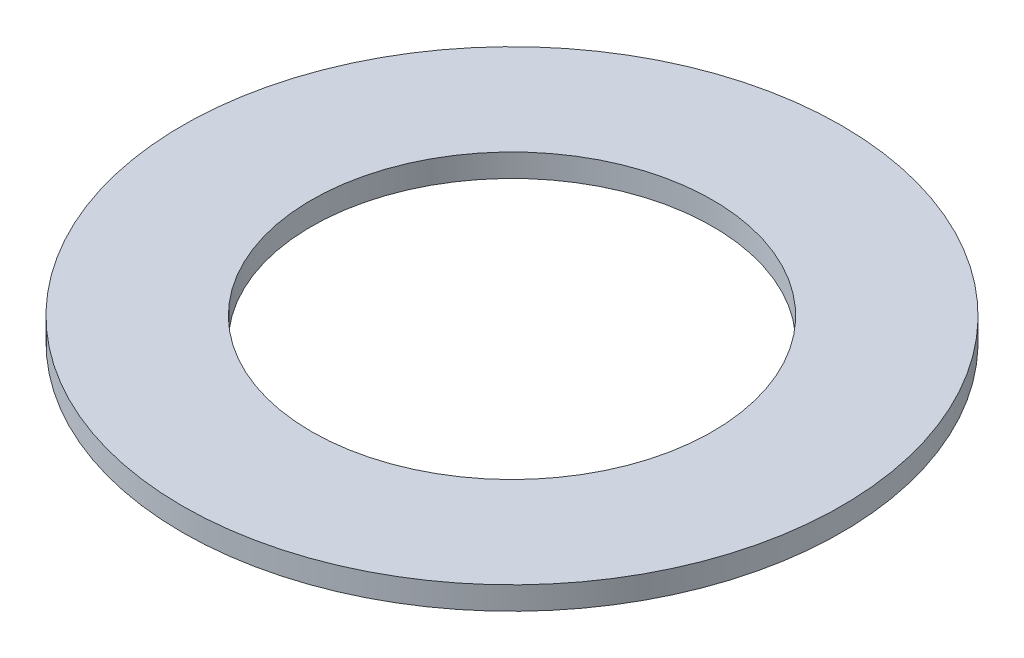
SolidWorks part; units mm, degrees
ref_plane "Front Plane" through (0, 0, 0) normal (0, 0, 1) x (1, 0, 0)
ref_plane "Top Plane" through (0, 0, 0) normal (0, 1, 0) x (1, 0, 0)
ref_plane "Right Plane" through (0, 0, 0) normal (1, 0, 0) x (0, 0, -1)
sketch "Sketch1" plane through (0, 0, 0) normal (0, 1, 0) x (1, 0, 0)
  circle A0 centre (0, 0) radius 57.5
  dimension "FLANGE_OD" = 115
extrude "Boss-Extrude1" add sketch "Sketch1" along normal blind 4
sketch "Sketch2" plane through (0, 0, 0) normal (0, 1, 0) x (1, 0, 0)
  circle A0 centre (0, 0) radius 35
  dimension "BORE_D" = 70
extrude "Cut-Extrude1" cut sketch "Sketch2" along normal through all
sketch "Sketch3" plane through (0, 4, 0) normal (0, 1, 0) x (1, 0, 0)
  circle A0 centre (0, 0) radius 22.521 construction
  circle A1 centre (-22.521, 0) radius 1.6568
  dimension "BOLT_D" = 3.3135
  dimension "BOLT_PCD" = 45.042
extrude "Cut-Extrude2" cut sketch "Sketch3" against normal blind 2.5327 rebuild error yes
pattern_circular "CirPattern1" count 8 over 360 rebuild error yes
